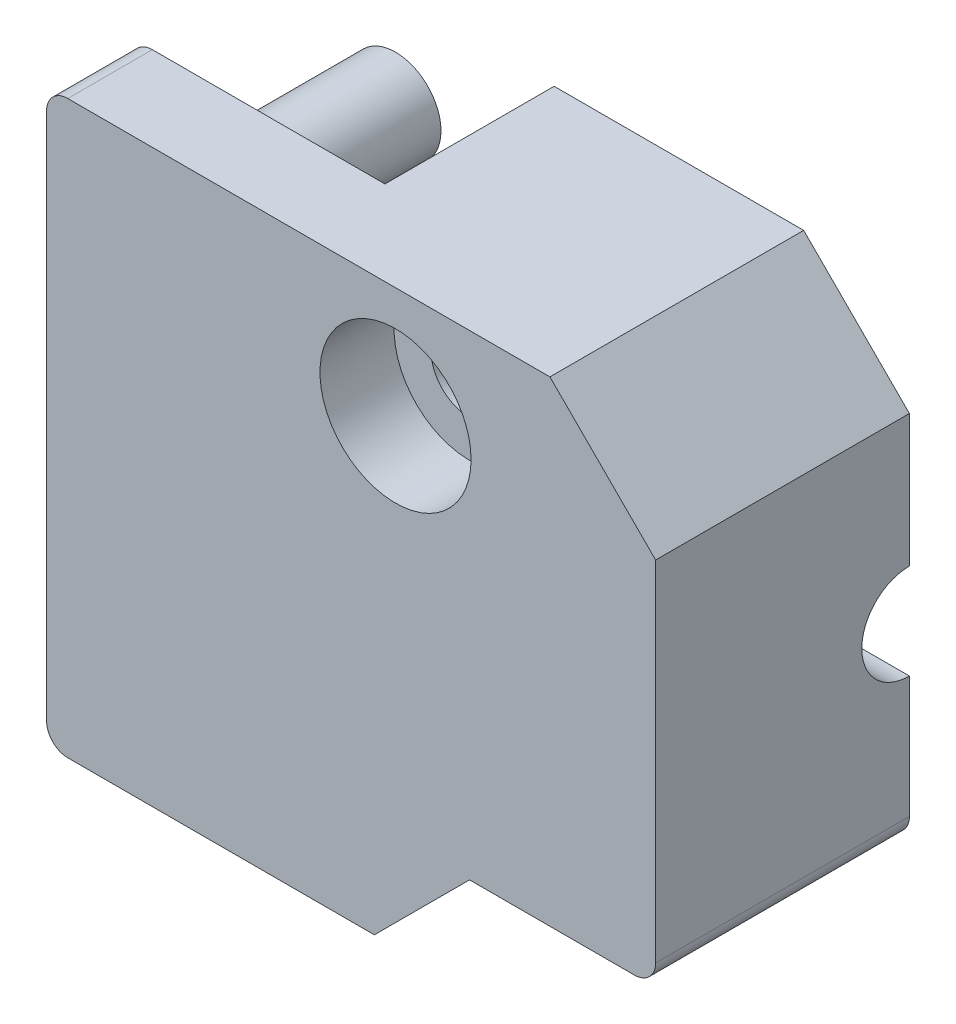
SolidWorks part; units mm, degrees
material "ABS"
ref_plane "Front Plane" through (0, 0, 0) normal (0, 0, 1) x (1, 0, 0)
ref_plane "Top Plane" through (0, 0, 0) normal (0, 1, 0) x (1, 0, 0)
ref_plane "Right Plane" through (0, 0, 0) normal (1, 0, 0) x (0, 0, -1)
sketch "Sketch2" plane through (0, 0, 0) normal (0, 0, 1) x (1, 0, 0)
  line L0 (15.5, 0) -> (20, 4.5)
  line L1 (1, 0) -> (15.5, 0)
  line L2 (0, 1) -> (0, 26)
  line L3 (1, 27) -> (20, 27)
  line L4 (20, 4.5) -> (20, 27)
  arc A0 (1, 0) -> (0, 1) centre (1, 1) cw
  arc A1 (1, 27) -> (0, 26) centre (1, 26) ccw
  point P3 (20, 0)
  point P6 (0, 0)
  point P10 (0, 27)
  dimension "D2" = 1
  dimension "D1" = 27
  dimension "D3" = 20
extrude "Boss-Extrude1" add sketch "Sketch2" along normal blind 4
sketch "Sketch3" plane through (0, 0, 0) normal (0, 0, 1) x (1, 0, 0)
  line L0 (4.5, 4.5) -> (4.5, 22.5) construction
  line L1 (1, 0) -> (15.5, 0) construction
  line L2 (0, 26) -> (0, 1) construction
  line L3 (3.5, 15.067) -> (3.5, 11.933)
  line L4 (0, 26) -> (0, 1) construction
  line L5 (12, 27) -> (12, 22.5)
  line L6 (20, 27) -> (1, 27) construction
  line L7 (20, 4.5) -> (15.2819, 4.5)
  circle A0 centre (4.5, 22.5) radius 2.15
  circle A1 centre (4.5, 4.5) radius 2.15
  circle A2 centre (4.5, 22.5) radius 7.5
  circle A3 centre (4.5, 4.5) radius 7.5
  arc A4 (11.5317, 7.1087) -> (3.5, 11.933) centre (4.5, 4.5) ccw
  arc A5 (11.5317, 7.1087) -> (15.2819, 4.5) centre (15.2819, 8.5) ccw
  point P23 (12, 4.5)
  line M13 (20, 27) -> (20, 4.5)
  line M14 (15.5, 0) -> (1, 0)
  line M18 (1, 27) -> (20, 27)
  dimension "D1" = 4.3
  dimension "D2" = 4.3
  dimension "D6" = 15
  dimension "D7" = 15
  dimension "D9" = 4
  dimension "D3" = 18
  dimension "D4" = 4.5
  dimension "D5" = 4.5
  dimension "D8" = 3.5
extrude "Boss-Extrude2" add sketch "Sketch3" against normal blind 8 contours A0 | A1
extrude "Boss-Extrude3" add sketch "Sketch3<3>" against normal up to surface (8 mm away) contours A3 L0 A2 M18 M13 M14 region at (14.6419, 15.3709, 0) up to face at (6.65, 22.5, -8)
sketch "Sketch3<3>" plane through (0, 0, 0) normal (0, 0, 1) x (1, 0, 0) same geometry as "Sketch3"
sketch "Sketch4" plane through (4.5, 0, 0) normal (1, 0, 0) x (0, 0, -1)
  line L0 (8, 4.5) -> (8, 27) construction
  line L2 (8, 15) -> (8, 12) construction
  line L3 (14.35, 7.15) -> (14.35, 19.85)
  line L4 (14.35, 7.15) -> (1.65, 7.15)
  line L5 (14.35, 19.85) -> (1.65, 19.85)
  line L6 (1.65, 7.15) -> (1.65, 19.85)
  line L7 (14.35, 7.15) -> (1.65, 19.85) construction
  line L8 (14.35, 19.85) -> (1.65, 7.15) construction
  circle A0 centre (8, 13.5) radius 7.5 construction
  circle A1 centre (8, 13.5) radius 6.35 construction
  circle A2 centre (8, 13.5) radius 2.25
  dimension "D1" = 15
  dimension "D2" = 12.7
  dimension "D3" = 4.5
  dimension "D4" = 12.7
  dimension "D5" = 12.7
extrude "Cut-Extrude2" cut sketch "Sketch4" along normal up to surface (15.5 mm away) contours A2 up to face at (20, 13.5, -1.6)
extrude "Cut-Extrude3" cut sketch "Sketch4<4>" along normal offset from surface (8.5 mm away) 7 up to face at (20, 13.5, -3.1071)
sketch "Sketch4<4>" plane through (4.5, 0, 0) normal (1, 0, 0) x (0, 0, -1) same geometry as "Sketch4"
sketch "Sketch5" plane through (20, 0, 0) normal (1, 0, 0) x (0, 0, -1)
  line L0 (8, 4.5) -> (0, 4.5) construction
  line L1 (1.45, 9.745) -> (14.55, 9.745)
  line L2 (1.45, 9.745) -> (1.45, 4.5)
  line L3 (1.45, 4.5) -> (14.55, 4.5)
  line L4 (14.55, 9.745) -> (14.55, 4.5)
  circle A0 centre (8, 13.5) radius 7.55
  line M2 (8, 15.75) -> (8, 27)
  line M3 (8, 27) -> (-4, 27)
  line M4 (-4, 27) -> (-4, 4.5)
  line M5 (-4, 4.5) -> (0, 4.5)
  line M6 (0, 4.5) -> (8, 4.5)
  dimension "D1" = 15.1
  dimension "D2" = 13.1
extrude "Boss-Extrude4" add sketch "Sketch5" along normal blind 5.8 contours A0 L2 M2 M3 M4 M5 M6 region at (20, 17.9761, -0.2693)
sketch "Sketch8" plane through (25.8, 0, 0) normal (1, 0, 0) x (0, 0, -1)
  line L0 (8, 4.5) -> (1.45, 4.5) construction
  line L1 (-4, 27) -> (8, 27)
  line L2 (-4, 27) -> (-4, 4.5)
  line L3 (-4, 4.5) -> (8, 4.5)
  line L4 (8, 27) -> (8, 4.5)
  line L5 (8, 4.5) -> (1.45, 4.5)
  circle A0 centre (8, 13.5) radius 2.25
  arc M1 (1.45, 9.745) -> (8, 21.05) centre (8, 13.5) cw
  line M2 (8, 21.05) -> (8, 27)
  line M3 (8, 27) -> (-4, 27)
  line M4 (-4, 27) -> (-4, 4.5)
  line M5 (-4, 4.5) -> (1.45, 4.5)
  line M6 (1.45, 4.5) -> (1.45, 9.745)
  dimension "D1" = 4.5
extrude "Boss-Extrude7" add sketch "Sketch8" along normal blind 3 contours M6 M1 M2 M3 M4 M5 | A0 L4 L3 M1 M6 region at (25.8, 17.9761, -0.2693) region at (25.8, 12.2241, -4.4746)
sketch "Sketch9" plane through (0, 0, 4) normal (0, 0, 1) x (1, 0, 0)
  line L0 (16.5, 15.75) -> (16.5, 21.75)
  line L10 (11.5162, 19.85) -> (13, 19.85)
  line L11 (12, 27) -> (12, 22.5)
  line L12 (28.8, 27) -> (12, 27)
  line L13 (28.8, 15.75) -> (28.8, 27)
  line L14 (25.8, 15.75) -> (28.8, 15.75)
  line L15 (25.8, 21.05) -> (25.8, 15.75)
  line L16 (20, 21.05) -> (25.8, 21.05)
  line L17 (20, 15.75) -> (20, 21.05)
  line L18 (13, 15.75) -> (20, 15.75)
  line L19 (13, 19.85) -> (13, 15.75)
  line L20 (11.5162, 19.85) -> (13, 19.85)
  line L21 (12, 27) -> (12, 22.5)
  line L22 (28.8, 27) -> (12, 27)
  line L23 (28.8, 15.75) -> (28.8, 27)
  line L24 (25.8, 15.75) -> (28.8, 15.75)
  line L25 (25.8, 21.05) -> (25.8, 15.75)
  line L26 (20, 21.05) -> (25.8, 21.05)
  line L27 (20, 15.75) -> (20, 21.05)
  line L28 (13, 15.75) -> (20, 15.75)
  line L29 (13, 19.85) -> (13, 15.75)
  arc A1 (11.5162, 19.85) -> (12, 22.5) centre (4.5, 22.5) ccw
  arc A2 (11.5162, 19.85) -> (12, 22.5) centre (4.5, 22.5) ccw
  dimension "D2" = 6
  dimension "D1" = 0
hole_wizard "CBORE for #6 Socket Head Cap Screw1" positions "Sketch11" profile "Sketch10" counterbore size "#6" standard "ANSI Inch" end condition through all
sketch "Sketch11" plane through (0, 0, 4) normal (0, 0, 1) x (1, 0, 0)
  point P0 (16.5, 21.75)
sketch "Sketch10" plane through (16.5, 21.75, 4) normal (1, 0, 0) x (0, -1, 0)
  line L0 (0, 0) -> (0, 12)
  line L1 (0, 12) -> (1.8288, 12)
  line L3 (1.8288, 12) -> (1.8288, 3.5052)
  line L4 (1.8288, 3.5052) -> (3.5725, 3.5052)
  line L5 (3.5725, 3.5052) -> (3.5725, 0)
  line L7 (3.5725, 0) -> (0, 0)
  line L11 (0, -6.35) -> (0, 107.95) construction
  dimension "Thru Hole Dia." = 3.6576
  dimension "Thru Hole Depth" = 12
  dimension "C'Bore Dia." = 7.145
  dimension "C'Bore Depth" = 3.5052
sketch "Sketch12" plane through (0, 0, -8) normal (0, 0, -1) x (-1, 0, 0)
  line L0 (-16.5, 11.25) -> (-16.5, 7.875)
  line L1 (-20, 11.25) -> (-13, 11.25) construction
  line L2 (-16.5, 7.875) -> (-20, 7.875)
  line L3 (-20, 4.5) -> (-20, 11.25) construction
  circle A0 centre (-16.5, 7.875) radius 1.75
  dimension "D1" = 3.5
extrude "Boss-Extrude8" add sketch "Sketch12" along normal blind 2 contours A0
chamfer "Chamfer1" distance 5 angle 45 1 edges at (28.8, 27, -2)
fillet "Fillet1" radius 1 1 edges at (28.8, 4.5, -2)
